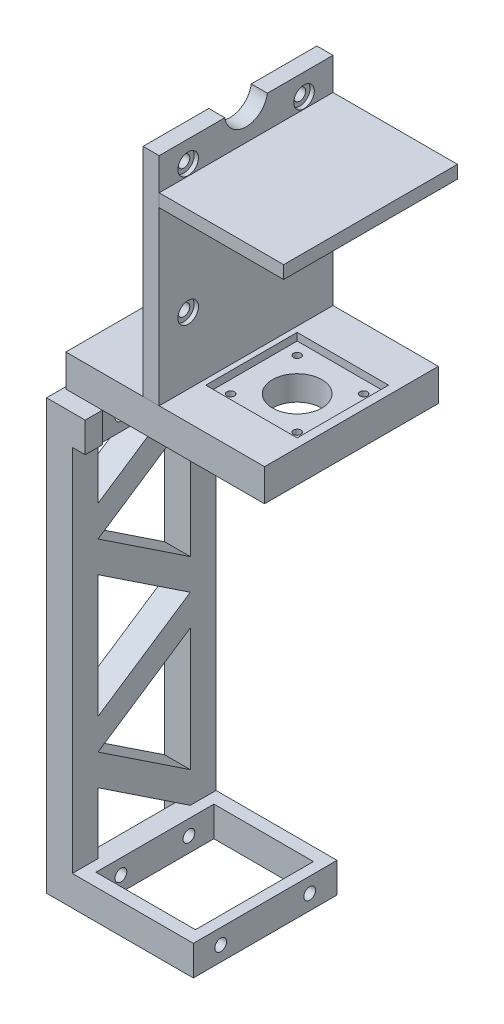
SolidWorks part; units mm, degrees
note: The reader was unsure of these and kept them because the rebuilt part matched: shared geometry of "Sketch11<5>", "Sketch13<3>".
ref_plane "Front Plane" through (0, 0, 0) normal (0, 0, 1) x (1, 0, 0)
ref_plane "Top Plane" through (0, 0, 0) normal (0, 1, 0) x (1, 0, 0)
ref_plane "Right Plane" through (0, 0, 0) normal (1, 0, 0) x (0, 0, -1)
sketch "Sketch1" plane through (0, 0, 0) normal (0, 1, 0) x (1, 0, 0)
  line L1 (-23.2, -27.5) -> (23.2, -27.5)
  line L2 (-23.2, -27.5) -> (-23.2, 27.5)
  line L3 (-23.2, 27.5) -> (23.2, 27.5)
  line L4 (23.2, -27.5) -> (23.2, 27.5)
  line L5 (-23.2, -27.5) -> (23.2, 27.5) construction
  line L6 (-23.2, 27.5) -> (23.2, -27.5) construction
  line L7 (-28.2, -33.5) -> (28.2, -33.5)
  line L8 (-28.2, -33.5) -> (-28.2, 33.5)
  line L9 (-28.2, 33.5) -> (28.2, 33.5)
  line L10 (28.2, -33.5) -> (28.2, 33.5)
  line L11 (-28.2, -33.5) -> (28.2, 33.5) construction
  line L12 (-28.2, 33.5) -> (28.2, -33.5) construction
  circle A0 centre (-2.9, 0) radius 4
  circle A1 centre (43.1, 0) radius 4
  point P0 (0, 0)
  point P6 (0, 0)
  dimension "D3" = 8
  dimension "D1" = 20.3
  dimension "D2" = 14.9
  dimension "D4" = 46
  dimension "D5" = 5
  dimension "D6" = 6
  dimension "D7" = 55
extrude "Boss-Extrude1" add sketch "Sketch1" along normal blind 14 contours L7 L10 L9 L8 L4 L1 L2 L3
sketch "Sketch4" plane through (0, 0, 0) normal (0, 1, 0) x (1, 0, 0)
  line L0 (-28.2, -33.5) -> (-40.2, -33.5)
  line L1 (-40.2, -33.5) -> (-40.2, -21.5)
  line L2 (-40.2, -21.5) -> (-28.2, -21.5)
  line L3 (-28.2, -33.5) -> (-28.2, 33.5) construction
  line L4 (-28.2, -21.5) -> (-28.2, -33.5)
  line L5 (-28.2, 33.5) -> (-40.2, 33.5)
  line L6 (-40.2, 33.5) -> (-40.2, 21.5)
  line L7 (-40.2, 21.5) -> (-28.2, 21.5)
  line L8 (-28.2, 21.5) -> (-28.2, 33.5)
  dimension "D1" = 12
  dimension "D2" = 12
extrude "Boss-Extrude2" add sketch "Sketch4" along normal blind 200
sketch "Sketch16" plane through (0, 0, -21.5) normal (0, 0, 1) x (1, 0, 0)
  line L0 (-40.2, 0) -> (-28.2, 0) construction
  line L1 (-28.2, 14) -> (-32.8, 14)
  line L2 (-28.2, 14) -> (-28.2, 0)
  line L3 (-28.2, 0) -> (-32.8, 0)
  line L4 (-32.8, 14) -> (-32.8, 0)
  dimension "D1" = 4.6
extrude "Boss-Extrude11" add sketch "Sketch16" along normal up to surface (43 mm away) up to face at (-33, 82.8, 21.5)
sketch "Sketch5" plane through (0, 200, 0) normal (0, 1, 0) x (1, 0, 0)
  line L0 (-28.2, -33.5) -> (28.2, -33.5) construction
  line L1 (-28.2, 33.5) -> (-23.2, 33.5)
  line L2 (-28.2, 33.5) -> (-28.2, -33.5)
  line L3 (-28.2, -33.5) -> (-23.2, -33.5)
  line L4 (-23.2, 33.5) -> (-23.2, -33.5)
  line L7 (-23.2, -27.5) -> (-23.2, 27.5) construction
extrude "Boss-Extrude3" add sketch "Sketch5" against normal blind 14
sketch "Sketch6" plane through (-40.2, 0, 0) normal (-1, 0, 0) x (0, 0, 1)
  line L0 (-21.5, 186) -> (21.5, 157.4103)
  line L1 (21.5, 200) -> (21.5, 0) construction
  line L2 (-21.5, 171.5897) -> (21.5, 143)
  line L3 (21.5, 143) -> (-21.5, 114.4103)
  line L4 (-21.5, 200) -> (-21.5, 0) construction
  line L5 (21.5, 128.5897) -> (-21.5, 100)
  line L6 (21.5, 157.4103) -> (21.5, 143)
  line L7 (21.5, 128.5897) -> (21.5, 143)
  line L8 (-21.5, 114.4103) -> (-21.5, 100)
  line L9 (-21.5, 186) -> (-21.5, 171.5897)
  line L10 (-21.5, 100) -> (21.5, 71.4103)
  line L11 (21.5, 71.4103) -> (21.5, 57)
  line L12 (21.5, 57) -> (-21.5, 85.5897)
  line L13 (-21.5, 85.5897) -> (-21.5, 100)
  line L14 (21.5, 57) -> (-21.5, 28.4103)
  line L15 (-21.5, 28.4103) -> (-21.5, 14)
  line L16 (-21.5, 14) -> (21.5, 42.5897)
  line L17 (21.5, 42.5897) -> (21.5, 57)
  line L18 (-21.5, 200) -> (-21.5, 186) construction
  line M18 (-21.5, 0) -> (-21.5, 200)
  dimension "D1" = 12
extrude "Boss-Extrude4" add sketch "Sketch6" against normal up to surface (12 mm away) contours L6 L0 L2 M18 | L5 L7 L3 M18 | L12 L11 L10 M18 | L16 L17 L14 M18 up to face at (-28.2, 100, 27.5)
sketch "Sketch2" plane through (28.2, 0, 0) normal (1, 0, 0) x (0, 0, -1)
  line L0 (-20.75, 7) -> (20.75, 7) construction
  line L1 (33.5, 14) -> (33.5, 0) construction
  circle A0 centre (-20.75, 7) radius 2.75
  circle A1 centre (20.75, 7) radius 2.75
  point P4 (33.5, 7)
  point P5 (0, 7)
  dimension "D1" = 5.5
  dimension "D2" = 41.5
extrude "Cut-Extrude1" cut sketch "Sketch2" against normal up to surface (5 mm away) up to face at (23.2, 7, 0)
sketch "Sketch3" plane through (-23.2, 0, 0) normal (1, 0, 0) x (0, 0, -1)
  line L0 (15.85, 7) -> (-15.85, 7) construction
  line L1 (-33.5, 14) -> (-33.5, 0) construction
  line L3 (-15.85, 7) -> (-33.5, 7) construction
  circle A0 centre (15.85, 7) radius 2.75
  circle A1 centre (-15.85, 7) radius 2.75
  point P0 (0, 7)
  dimension "D2" = 5.5
  dimension "D1" = 31.7
extrude "Cut-Extrude2" cut sketch "Sketch3" against normal through all
sketch "Sketch7" plane through (-23.2, 0, -32.7) normal (1, 0, 0) x (0, 0, -1)
  line L0 (-16.85, 193) -> (-48.55, 193) construction
  line L1 (-66.2, 200) -> (0.8, 200) construction
  line L2 (-66.2, 186) -> (-66.2, 200) construction
  line L3 (-48.55, 193) -> (-66.2, 193) construction
  circle A0 centre (-16.85, 193) radius 2.75
  circle A1 centre (-48.55, 193) radius 2.75
  point P0 (-32.7, 193)
  point P7 (-32.7, 200)
  point P13 (-66.2, 193)
  dimension "D2" = 5.5
  dimension "D1" = 31.7
extrude "Cut-Extrude3" cut sketch "Sketch7" against normal through all
ref_plane "Plane1" through (0, 215, 0) normal (0, 1, 0) x (1, 0, 0)
sketch "Sketch8" plane through (-23.2, 0, 0) normal (1, 0, 0) x (0, 0, -1)
  line L0 (-33.5, 186) -> (33.5, 186) construction
  line L1 (-33.5, 200) -> (-25.5, 200)
  line L2 (-33.5, 200) -> (-33.5, 186)
  line L3 (-33.5, 186) -> (-25.5, 186)
  line L4 (-25.5, 200) -> (-25.5, 186)
  line L6 (33.5, 200) -> (25.5, 200)
  line L7 (33.5, 200) -> (33.5, 186)
  line L8 (33.5, 186) -> (25.5, 186)
  line L9 (25.5, 200) -> (25.5, 186)
  dimension "D1" = 8
extrude "Boss-Extrude5" add sketch "Sketch8" along normal blind 1
sketch "Sketch9" plane through (0, 215, 0) normal (0, 1, 0) x (1, 0, 0)
  line L0 (-28.2, 21.5) -> (-28.2, -21.5) construction
  line L1 (-24.2, 40.5) -> (68.4, 40.5)
  line L2 (-24.2, 40.5) -> (-24.2, -40.5)
  line L3 (-24.2, -40.5) -> (68.4, -40.5)
  line L4 (68.4, 40.5) -> (68.4, -40.5)
  line L5 (-23.2, -25.5) -> (-23.2, 25.5) construction
  line L6 (-40.2, 33.5) -> (-40.2, 21.5) construction
  line L7 (-22.2, 40.5) -> (-15.4135, 40.5)
  line L8 (-22.2, 40.5) -> (-22.2, -40.5)
  line L9 (-22.2, -40.5) -> (-15.4135, -40.5)
  line L10 (-15.4135, 40.5) -> (-15.4135, -40.5)
  line L11 (-22.2, 33.5) -> (-22.2, 25.5) construction
  point P5 (68.4, 0)
  point P9 (-28.2, 0)
  point P10 (-24.2, 0)
  point P13 (43.1, 0)
  point P26 (-15.4135, 0)
  dimension "D1" = 81
  dimension "D2" = 25.3
  dimension "D3" = 66.3
  dimension "D4" = 81
  dimension "D5" = 16
extrude "Boss-Extrude6" add sketch "Sketch9" along normal blind 15 separate body contours L7 L10 L9 L8 L3 L2 L1 | L8 L1 L2 L3 | L1 L8 L3 L4
sketch "Sketch10" plane through (0, 230, 0) normal (0, 1, 0) x (1, 0, 0)
  line L1 (21.8, -21.3) -> (64.4, -21.3)
  line L2 (21.8, -21.3) -> (21.8, 21.3)
  line L3 (21.8, 21.3) -> (64.4, 21.3)
  line L4 (64.4, -21.3) -> (64.4, 21.3)
  line L5 (21.8, -21.3) -> (64.4, 21.3) construction
  line L6 (21.8, 21.3) -> (64.4, -21.3) construction
  line L8 (68.4, 40.5) -> (68.4, -40.5) construction
  point P0 (43.1, 0)
  point P13 (68.4, 0)
  dimension "D1" = 42.6
  dimension "D2" = 42.6
  dimension "D3" = 4
extrude "Cut-Extrude4" cut sketch "Sketch10" against normal blind 3.5
sketch "Sketch11" plane through (0, 226.5, -221.5) normal (0, -1, 0) x (1, 0, 0)
  line L0 (64.4, 200.2) -> (21.8, 200.2) construction
  line L1 (27.6, 206) -> (58.6, 206) construction
  line L2 (27.6, 206) -> (27.6, 237) construction
  line L3 (27.6, 237) -> (58.6, 237) construction
  line L4 (58.6, 206) -> (58.6, 237) construction
  line L5 (27.6, 206) -> (58.6, 237) construction
  line L6 (27.6, 237) -> (58.6, 206) construction
  line L7 (64.4, 242.8) -> (64.4, 200.2) construction
  circle A0 centre (27.6, 237) radius 1.75
  circle A1 centre (58.6, 237) radius 1.75
  circle A2 centre (58.6, 206) radius 1.75
  circle A3 centre (27.6, 206) radius 1.75
  circle A4 centre (27.6, 237) radius 3
  circle A5 centre (58.6, 237) radius 3
  circle A6 centre (58.6, 206) radius 3
  circle A7 centre (27.6, 206) radius 3
  circle A8 centre (43.1, 221.5) radius 11.5
  point P0 (43.1, 221.5)
  point P17 (43.1, 200.2)
  point P21 (64.4, 221.5)
  dimension "D1" = 3.5
  dimension "D4" = 6
  dimension "D5" = 23
  dimension "D2" = 31
  dimension "D3" = 31
extrude "Cut-Extrude5" cut sketch "Sketch11" along normal up to surface (11.5 mm away) contours A1 | A0 | A3 | A2 | A8
extrude "Cut-Extrude6" cut sketch "Sketch11<5>" against normal blind 3 from surface
sketch "Sketch11<5>" plane through (0, 226.5, -221.5) normal (0, -1, 0) x (1, 0, 0) same geometry as "Sketch11"
ref_plane "Plane2" through (11.8, 0, 0) normal (-1, 0, 0) x (0, 0, 1)
sketch "Sketch13" plane through (11.8, 0, 0) normal (-1, 0, 0) x (0, 0, 1)
  line L0 (0, 332.3723) -> (0, 342.9574) construction
  line L1 (-27, 261) -> (27, 261) construction
  line L2 (-27, 261) -> (-27, 321) construction
  line L3 (-27, 321) -> (27, 321) construction
  line L4 (27, 261) -> (27, 321) construction
  line L5 (-27, 261) -> (27, 321) construction
  line L6 (-27, 321) -> (27, 261) construction
  line L7 (-40.5, 331) -> (40.5, 331)
  line L8 (-40.5, 331) -> (-40.5, 230)
  line L9 (-40.5, 230) -> (40.5, 230)
  line L10 (40.5, 331) -> (40.5, 230)
  line L11 (-10, 332.3723) -> (-10, 342.9574)
  line L12 (10, 332.3723) -> (10, 342.9574)
  line L14 (25.5, 200) -> (-25.5, 200) construction
  line L16 (-40.5, 230) -> (40.5, 230) construction
  circle A0 centre (-27, 321) radius 2.75
  circle A1 centre (27, 321) radius 2.75
  circle A2 centre (27, 261) radius 2.75
  circle A3 centre (-27, 261) radius 2.75
  arc A4 (-10, 332.3723) -> (10, 332.3723) centre (0, 332.3723) ccw
  arc A5 (10, 342.9574) -> (-10, 342.9574) centre (0, 342.9574) ccw
  circle A6 centre (27, 321) radius 4.8
  circle A7 centre (27, 261) radius 4.8
  circle A8 centre (-27, 261) radius 4.8
  circle A9 centre (-27, 321) radius 4.8
  point P0 (0, 291)
  point P14 (0, 331)
  point P15 (0, 337.6649)
  point P32 (0, 200)
  dimension "D1" = 5.5
  dimension "D7" = 9.6
  dimension "D2" = 54
  dimension "D3" = 60
  dimension "D4" = 81
  dimension "D5" = 10
  dimension "D6" = 20
  dimension "D8" = 101
extrude "Boss-Extrude7" add sketch "Sketch13" against normal blind 5.5 separate body contours L10 L7 L8 L9 A3 L2 A0 L3 A1 L4 A2 L1 | A9 A0 | A6 A1 | A7 A2 | A8 A3
extrude "Boss-Extrude10" add sketch "Sketch13<3>" against normal blind 2 from surface at -5.5 contours A4 L11 L7 L8 L9 L10 L12 A9 A8 A7 A6
sketch "Sketch13<3>" plane through (11.8, 0, 0) normal (-1, 0, 0) x (0, 0, 1) same geometry as "Sketch13"
sketch "Sketch15" plane through (19.3, 0, 0) normal (1, 0, 0) x (0, 0, -1)
  line L1 (-40.5, 316) -> (40.5, 316)
  line L2 (-40.5, 316) -> (-40.5, 310)
  line L3 (-40.5, 310) -> (40.5, 310)
  line L4 (40.5, 316) -> (40.5, 310)
  line L7 (40.5, 230) -> (-40.5, 230) construction
  line L8 (-40.5, 331) -> (-40.5, 230) construction
  line L9 (40.5, 331) -> (40.5, 230) construction
  dimension "D1" = 80
  dimension "D2" = 6
extrude "Boss-Extrude9" add sketch "Sketch15" along normal blind 58
